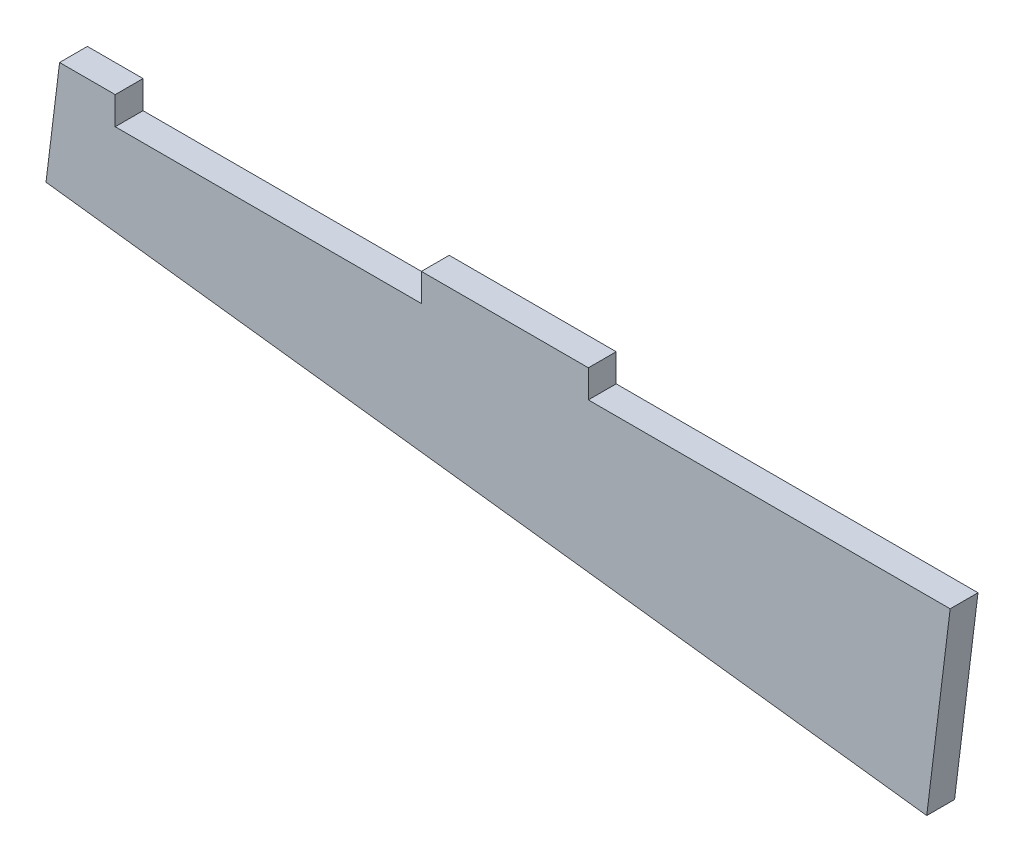
SolidWorks part; units mm, degrees
ref_plane "Front Plane" through (0, 0, 0) normal (0, 0, 1) x (1, 0, 0)
ref_plane "Top Plane" through (0, 0, 0) normal (0, 1, 0) x (1, 0, 0)
ref_plane "Right Plane" through (0, 0, 0) normal (1, 0, 0) x (0, 0, -1)
sketch "Sketch1" plane through (0, 0, 0) normal (0, 0, 1) x (1, 0, 0)
  line L0 (-195.3168, -62.6592) -> (-182.6168, -62.6592)
  line L4 (-182.6168, -62.6592) -> (-182.6168, -69.0092)
  line L5 (-182.6168, -69.0092) -> (-112.7668, -69.0092)
  line L6 (-112.7668, -69.0092) -> (-112.7668, -62.6592)
  line L7 (-112.7668, -62.6592) -> (-74.6668, -62.6592)
  line L8 (-74.6668, -62.6592) -> (-74.6668, -69.0092)
  line L9 (-74.6668, -69.0092) -> (7.8832, -69.0092)
  line L10 (7.8832, -69.0092) -> (2.5379, -112.5435)
  line L11 (2.5379, -112.5435) -> (-198.4122, -87.8699)
  line L12 (-198.4122, -87.8699) -> (-195.3168, -62.6592)
  line L13 (-378.8613, -54.018) -> (14.8387, -102.3582) construction
  dimension "D1" = 12.7
  dimension "D2" = 6.35
  dimension "D3" = 69.85
  dimension "D4" = 38.1
  dimension "D5" = 82.55
  dimension "D6" = 25.4
extrude "Boss-Extrude1" add sketch "Sketch1" against normal blind 6.35
